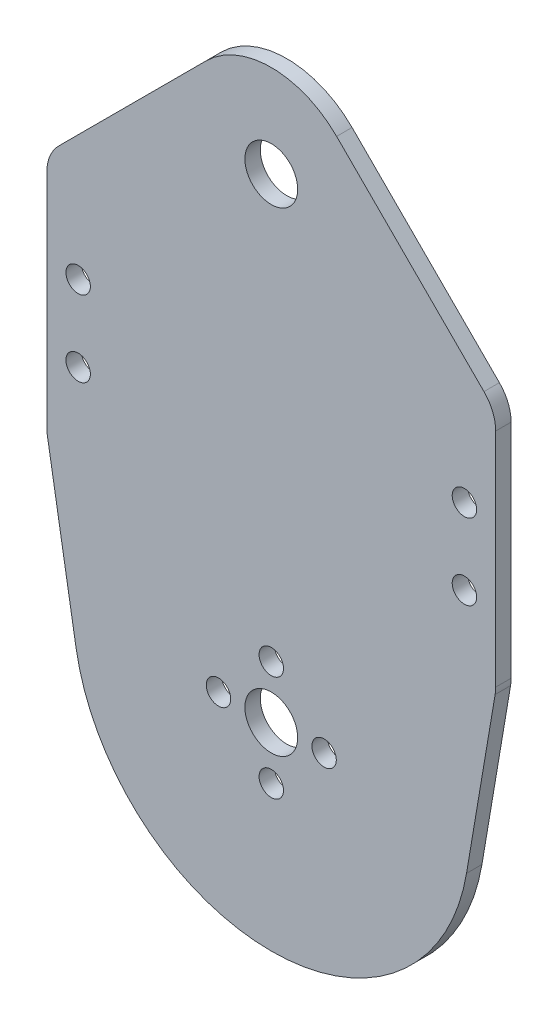
SolidWorks part; units mm, degrees
material "6061-T6 (SS)"
ref_plane "Front" through (0, 0, 0) normal (0, 0, 1) x (1, 0, 0)
ref_plane "Top" through (0, 0, 0) normal (0, 1, 0) x (1, 0, 0)
ref_plane "Right" through (0, 0, 0) normal (1, 0, 0) x (0, 0, -1)
ref_axis "side-side" through (80.9, 0, 0) along (-1, 0, 0)
ref_axis "up-down" through (0, 50, 0) along (0, -1, 0)
ref_axis "front-back" through (0, 0, -80.9) along (0, 0, 1)
sketch "Sketch1" plane through (0, 0, 0) normal (0, 0, 1) x (1, 0, 0)
  line L5 (0, -50) -> (0, 50) construction
  line L11 (-29.5799, -5.0029) -> (-33.9151, 20.6293)
  line L12 (-34, 21.6405) -> (-34, 55.2473)
  line L13 (-9.8995, 81.8595) -> (-32.224, 59.535)
  line L14 (32.224, 59.535) -> (9.8995, 81.8595)
  line L15 (34, 21.6405) -> (34, 55.2473)
  line L16 (29.5799, -5.0029) -> (33.9151, 20.6293)
  circle A1 centre (0, 0) radius 4
  circle A2 centre (0, 8) radius 1.85
  circle A3 centre (-8, 0) radius 1.85
  circle A4 centre (0, -8) radius 1.85
  circle A5 centre (8, 0) radius 1.85
  circle A6 centre (0, 0) radius 8 construction
  arc A12 (-34, 21.6405) -> (-33.9151, 20.6293) centre (-27.9363, 21.6405) ccw
  arc A13 (-32.224, 59.535) -> (-34, 55.2473) centre (-27.9363, 55.2473) ccw
  arc A14 (9.8995, 81.8595) -> (-9.8995, 81.8595) centre (0, 71.96) ccw
  arc A15 (34, 55.2473) -> (32.224, 59.535) centre (27.9363, 55.2473) ccw
  arc A16 (33.9151, 20.6293) -> (34, 21.6405) centre (27.9363, 21.6405) ccw
  arc A17 (-29.5799, -5.0029) -> (29.5799, -5.0029) centre (0, 0) ccw
  circle A19 centre (0, 71.96) radius 4
  circle A21 centre (-29.2625, 32) radius 1.85
  circle A23 centre (29.2625, 43.5) radius 1.85
  circle A25 centre (29.2625, 32) radius 1.85
  circle A27 centre (-29.2625, 43.5) radius 1.85
  point P0 (0, 0)
  dimension "D3" = 8
  dimension "D4" = 3.7
  dimension "D5" = 16
extrude "Boss-Extrude1" add sketch "Sketch1" along normal blind 2.3368
